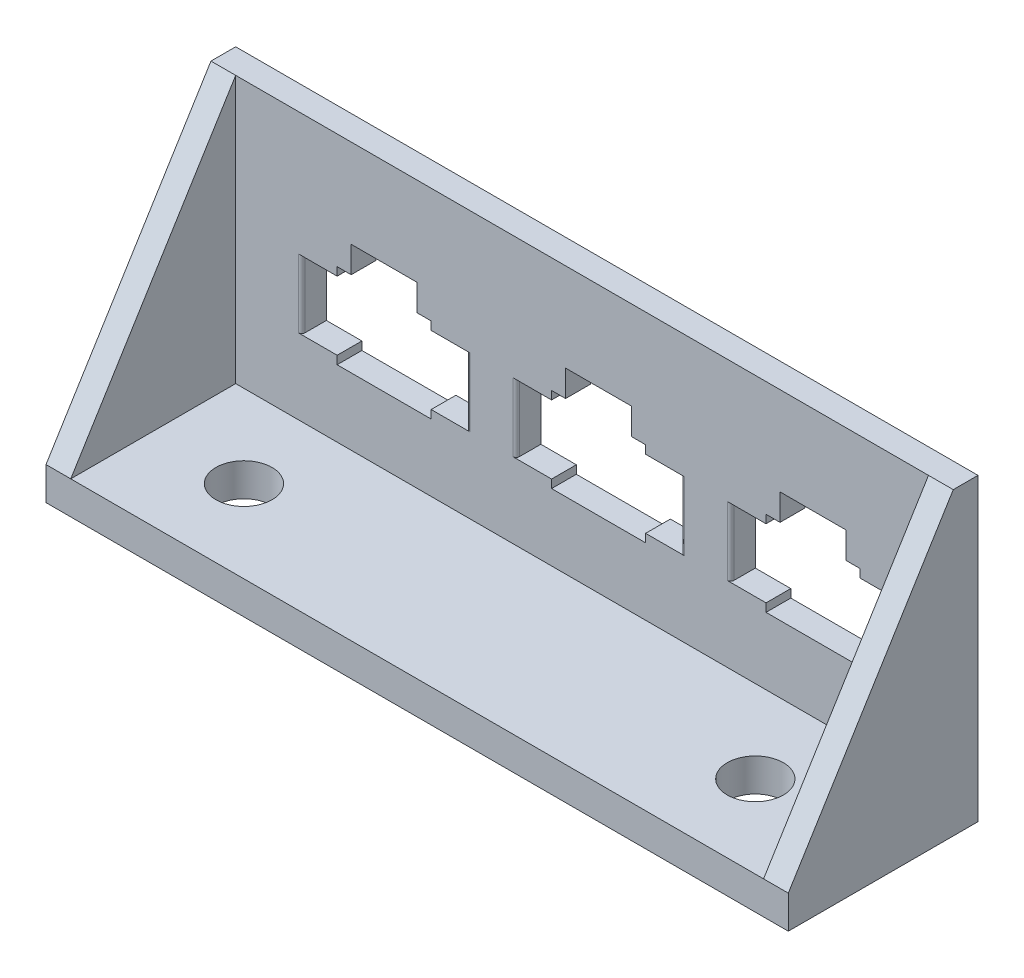
SolidWorks part; units mm, degrees
ref_plane "Front Plane" through (0, 0, 0) normal (0, 0, 1) x (1, 0, 0)
ref_plane "Top Plane" through (0, 0, 0) normal (0, 1, 0) x (1, 0, 0)
ref_plane "Right Plane" through (0, 0, 0) normal (1, 0, 0) x (0, 0, -1)
sketch "Sketch1" plane through (0, 0, 0) normal (0, 0, 1) x (1, 0, 0)
  line L0 (-27.1356, 52.5753) -> (-27.1356, 53.0753)
  line L2 (-27.1356, 52.5753) -> (-24.9856, 52.5753)
  line L3 (-27.9856, 53.0753) -> (-27.9856, 54.6753)
  line L4 (-14.1356, 52.5753) -> (-14.1356, 53.0753)
  line L5 (-27.1356, 48.4253) -> (-24.9856, 48.4253)
  line L6 (-14.1356, 52.5753) -> (-11.9856, 52.5753)
  line L7 (-32.8356, 52.5753) -> (-32.8356, 53.0753)
  line L8 (-27.9856, 53.0753) -> (-27.1356, 53.0753)
  line L9 (-14.9856, 53.0753) -> (-14.9856, 54.6753)
  line L10 (-14.1356, 48.4253) -> (-11.9856, 48.4253)
  line L11 (-19.8356, 52.5753) -> (-19.8356, 53.0753)
  line L12 (-14.9856, 53.0753) -> (-14.1356, 53.0753)
  line L13 (-31.9856, 53.0753) -> (-31.9856, 54.6753)
  line L14 (-18.9856, 53.0753) -> (-18.9856, 54.6753)
  line L15 (-21.9856, 52.5753) -> (-19.8356, 52.5753)
  line L16 (-21.9856, 52.5753) -> (-21.9856, 48.4253)
  line L17 (-21.9856, 48.4253) -> (-19.8356, 48.4253)
  line L18 (-11.9856, 52.5753) -> (-11.9856, 48.4253)
  line L19 (-19.8356, 47.9253) -> (-14.1356, 47.9253)
  line L20 (-19.8356, 47.9253) -> (-19.8356, 48.4253)
  line L21 (-19.8356, 53.0753) -> (-18.9856, 53.0753)
  line L22 (-14.1356, 47.9253) -> (-14.1356, 48.4253)
  line L23 (-18.9856, 54.6753) -> (-14.9856, 54.6753)
  line L24 (-16.9856, 44.8339) -> (-16.9856, 56.1666) construction
  line L25 (-34.0245, 50.5003) -> (0.0534, 50.5003) construction
  line L26 (-1.1356, 52.5753) -> (-1.1356, 53.0753)
  line L27 (-1.1356, 52.5753) -> (1.0144, 52.5753)
  line L28 (-1.9856, 53.0753) -> (-1.9856, 54.6753)
  line L29 (-1.1356, 48.4253) -> (1.0144, 48.4253)
  line L30 (-6.8356, 52.5753) -> (-6.8356, 53.0753)
  line L31 (-1.9856, 53.0753) -> (-1.1356, 53.0753)
  line L32 (-5.9856, 53.0753) -> (-5.9856, 54.6753)
  line L33 (-8.9856, 52.5753) -> (-6.8356, 52.5753)
  line L34 (-8.9856, 52.5753) -> (-8.9856, 48.4253)
  line L35 (-8.9856, 48.4253) -> (-6.8356, 48.4253)
  line L36 (1.0144, 52.5753) -> (1.0144, 48.4253)
  line L37 (-6.8356, 47.9253) -> (-1.1356, 47.9253)
  line L38 (-6.8356, 47.9253) -> (-6.8356, 48.4253)
  line L39 (-6.8356, 53.0753) -> (-5.9856, 53.0753)
  line L40 (-1.1356, 47.9253) -> (-1.1356, 48.4253)
  line L41 (-5.9856, 54.6753) -> (-1.9856, 54.6753)
  line L42 (-3.9856, 44.8339) -> (-3.9856, 56.1666) construction
  line L43 (-21.0245, 50.5003) -> (13.0534, 50.5003) construction
  line L44 (-29.9856, 44.8339) -> (-29.9856, 56.1666) construction
  line L45 (-34.9856, 52.5753) -> (-32.8356, 52.5753)
  line L46 (-34.9856, 52.5753) -> (-34.9856, 48.4253)
  line L47 (-34.9856, 48.4253) -> (-32.8356, 48.4253)
  line L48 (-24.9856, 52.5753) -> (-24.9856, 48.4253)
  line L50 (-38.9856, 60.044) -> (3.0144, 60.044)
  line L51 (-47.0245, 50.5003) -> (-12.9466, 50.5003) construction
  line L52 (-32.8356, 47.9253) -> (-27.1356, 47.9253)
  line L53 (-32.8356, 47.9253) -> (-32.8356, 48.4253)
  line L54 (-32.8356, 53.0753) -> (-31.9856, 53.0753)
  line L55 (-27.1356, 47.9253) -> (-27.1356, 48.4253)
  line L56 (-38.9856, 60.044) -> (-38.9856, 41.8604)
  line L57 (-38.9856, 41.8604) -> (3.0144, 41.8604)
  line L58 (3.0144, 60.044) -> (3.0144, 41.8604)
  line L60 (-31.9856, 54.6753) -> (-27.9856, 54.6753)
  point P3 (0, 0)
  point P17 (-16.9856, 50.5003)
  point P22 (-16.9856, 50.5003)
  point P25 (-16.9856, 50.5003)
  point P28 (-16.9856, 50.5003)
  point P41 (-3.9856, 50.5003)
  point P46 (-3.9856, 50.5003)
  point P47 (-29.9856, 50.5003)
  point P52 (-29.9856, 50.5003)
  point P55 (-29.9856, 50.5003)
  point P58 (-29.9856, 50.5003)
  point P67 (-3.9856, 50.5003)
  point P71 (-3.9856, 50.5003)
  dimension "D2" = 1.6
  dimension "D3" = 3
  dimension "D4" = 42
  dimension "D5" = 22
  dimension "D6" = 9
  dimension "D7" = 18.1836
  dimension "D13" = 4.15
  dimension "D14" = 5.15
  dimension "D15" = 4
  dimension "D17" = 5.7
  dimension "D18" = 10
extrude "Boss-Extrude1" add sketch "Sketch1" along normal blind 1.5
sketch "Sketch2" plane through (0, 0, 1.5) normal (0, 0, 1) x (1, 0, 0)
  line L0 (3.0144, 41.8604) -> (3.0144, 60.044) construction
  line L1 (-38.9856, 41.8604) -> (3.0144, 41.8604)
  line L2 (-38.9856, 41.8604) -> (-38.9856, 43.8604)
  line L3 (-38.9856, 43.8604) -> (3.0144, 43.8604)
  line L4 (3.0144, 41.8604) -> (3.0144, 43.8604)
  dimension "D1" = 2
extrude "Boss-Extrude2" add sketch "Sketch2" along normal blind 10
sketch "Sketch7" plane through (-38.9856, 0, 0) normal (-1, 0, 0) x (0, 0, 1)
  line L0 (11.5, 43.8604) -> (1.5, 60.044)
  line L6 (0, 60.044) -> (0, 41.8604)
  line L7 (0, 41.8604) -> (11.5, 41.8604)
  line L8 (11.5, 41.8604) -> (11.5, 43.8604)
  line L9 (11.5, 43.8604) -> (1.5, 43.8604)
  line L10 (1.5, 43.8604) -> (1.5, 60.044)
  line L11 (1.5, 60.044) -> (0, 60.044)
  line L12 (0, 60.044) -> (0, 41.8604)
  line L13 (0, 41.8604) -> (11.5, 41.8604)
  line L14 (11.5, 41.8604) -> (11.5, 43.8604)
  line L15 (11.5, 43.8604) -> (1.5, 43.8604)
  line L16 (1.5, 43.8604) -> (1.5, 60.044)
  line L17 (1.5, 60.044) -> (0, 60.044)
  line M7 (0, 60.044) -> (0, 41.8604)
  line M8 (0, 41.8604) -> (11.5, 41.8604)
  line M9 (11.5, 41.8604) -> (11.5, 43.8604)
  line M10 (11.5, 43.8604) -> (1.5, 43.8604)
  line M11 (1.5, 43.8604) -> (1.5, 60.044)
  line M12 (1.5, 60.044) -> (0, 60.044)
  dimension "D1" = 0
extrude "Boss-Extrude4" add sketch "Sketch7" along normal blind 1.5 contours M12 M7 M8 M9 M10 M11 | L0 M10 M11 region at (-38.9856, 49.2549, 4.8333) region at (-38.9856, 42.8604, 11.2849)
extrude "Boss-Extrude5" add sketch "Sketch7<3>" against normal blind 1.5 from offset 42 contours L0 M10 M11 | M12 M7 M8 M9 M10 M11 region at (-38.9856, 49.2549, 4.8333) region at (-38.9856, 42.8604, 11.2849) offset against normal yes
sketch "Sketch7<3>" plane through (-38.9856, 0, 0) normal (-1, 0, 0) x (0, 0, 1) same geometry as "Sketch7"
hole_wizard "M3 Clearance Hole2" positions "Sketch8" profile "Sketch9" hole size "M3" standard "ANSI Metric" end condition through all
sketch "Sketch8" plane through (0, 43.8604, 0) normal (0, 1, 0) x (1, 0, 0)
  line L0 (3.0144, -11.5) -> (3.0144, -1.5) construction
  line L1 (3.0144, -11.5) -> (-38.9856, -11.5) construction
  point P0 (-33.4856, -6.5)
  point P2 (-2.4856, -6.5)
  dimension "D1" = 31
  dimension "D2" = 5.5
  dimension "D3" = 5
sketch "Sketch9" plane through (-33.4856, 43.8604, 6.5) normal (1, 0, 0) x (0, 0, 1)
  line L0 (0, 0) -> (0, 2)
  line L1 (0, 2) -> (1.7, 2)
  line L2 (1.7, 2) -> (1.7, 0)
  line L5 (1.7, 0) -> (0, 0)
  line L11 (0, -6.35) -> (0, 107.95) construction
  dimension "Thru Hole Dia." = 3.4
  dimension "Thru Hole Depth" = 2
fillet "Fillet4" radius 0.2 6 edges at (-34.9856, 50.5003, 1.5) (-24.9856, 50.5003, 1.5) (-21.9856, 50.5003, 1.5) (-11.9856, 50.5003, 1.5) (-8.9856, 50.5003, 1.5) (1.0144, 50.5003, 1.5)
